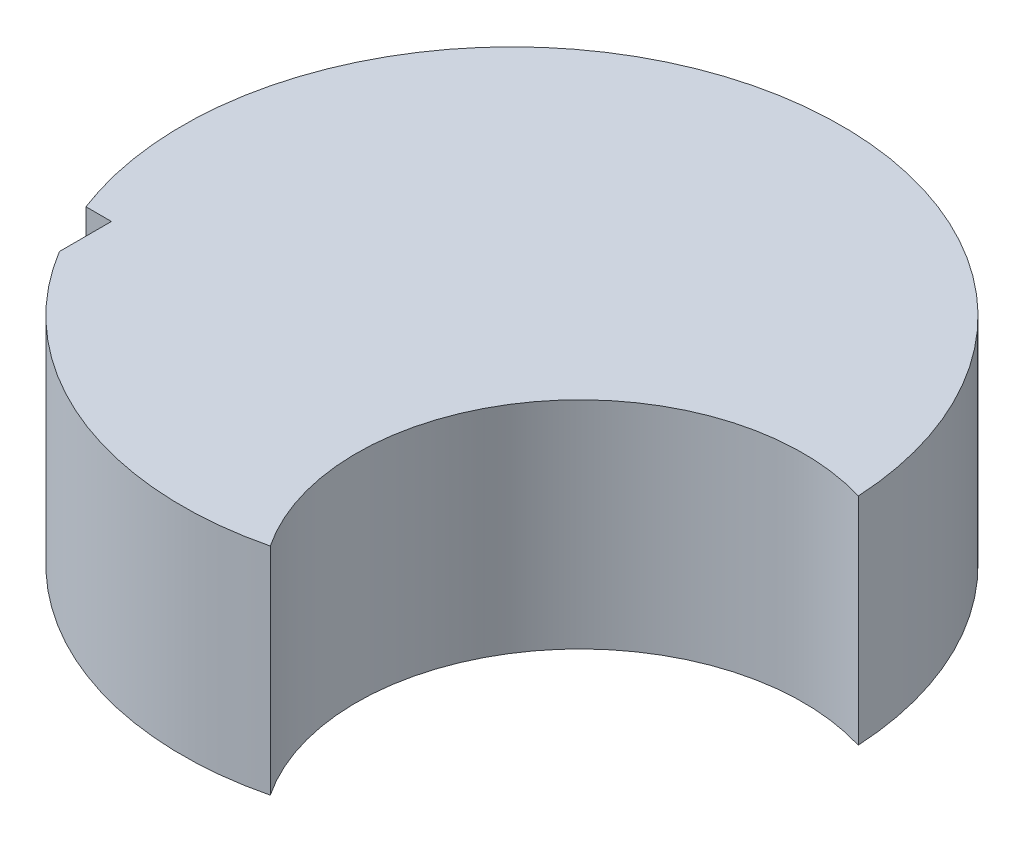
SolidWorks part; units mm, degrees
ref_plane "Front Plane" through (0, 0, 0) normal (0, 0, 1) x (1, 0, 0)
ref_plane "Top Plane" through (0, 0, 0) normal (0, 1, 0) x (1, 0, 0)
ref_plane "Right Plane" through (0, 0, 0) normal (1, 0, 0) x (0, 0, -1)
sketch "Sketch1" plane through (0, 0, 0) normal (0, 1, 0) x (1, 0, 0)
  arc A0 (92.9761, 4.8609) -> (22.1523, -90.4293) centre (0, 0) ccw
  arc A1 (92.9761, 4.8609) -> (22.1523, -90.4293) centre (74.7241, -55.5382) ccw
extrude "Boss-Extrude1" add sketch "Sketch1" along normal blind 60.96
ref_plane "Plane1" through (0, 137.16, 0) normal (0, 1, 0) x (1, 0, 0)
sketch "Sketch2" plane through (0, 137.16, 0) normal (0, 1, 0) x (1, 0, 0)
  point P0 (36.5712, 50.7694)
sketch "Sketch3" plane through (0, 60.96, 0) normal (0, 1, 0) x (1, 0, 0)
  line L1 (-120.6407, -33.4616) -> (-79.6791, -33.4616)
  line L2 (-120.6407, -33.4616) -> (-120.6407, -67.2117)
  line L3 (-120.6407, -67.2117) -> (-79.6791, -67.2117)
  line L4 (-79.6791, -33.4616) -> (-79.6791, -67.2117)
extrude "Cut-Extrude1" cut sketch "Sketch3" against normal up to next
ref_axis "Axis1" through (92.9761, 60.96, -4.8609) along (0, -1, 0)
ref_axis "Axis2" through (0, 144.018, 0) along (0, -1, 0)
ref_axis "Axis3" through (92.9761, 60.96, -4.8609) along (-0.5307, -0.4568, 0.714)
ref_axis "Axis4" through (74.7241, 60.96, 55.5382) along (0, -1, 0)
ref_axis "Axis5" through (36.5712, 137.16, -50.7694) along (0, 1, 0)
